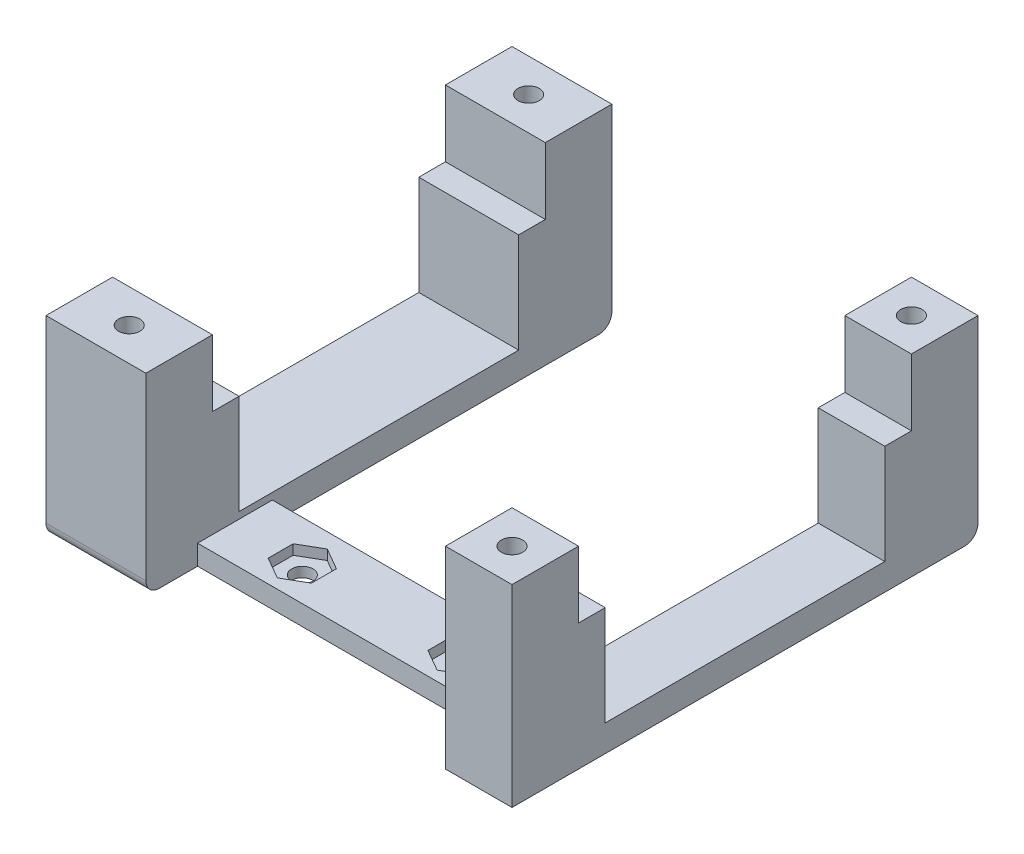
SolidWorks part; units mm, degrees
ref_plane "Alzado" through (0, 0, 0) normal (0, 0, 1) x (1, 0, 0)
ref_plane "Planta" through (0, 0, 0) normal (0, 1, 0) x (1, 0, 0)
ref_plane "Vista lateral" through (0, 0, 0) normal (1, 0, 0) x (0, 0, -1)
sketch "Croquis1" plane through (0, 0, 0) normal (0, 1, 0) x (1, 0, 0)
  line L0 (-10.4545, 22.1503) -> (-10.4545, -47.8497)
  line L1 (-25.4545, 22.1503) -> (-10.4545, 22.1503)
  line L2 (-25.4545, 22.1503) -> (-25.4545, -47.8497)
  line L3 (-25.4545, -47.8497) -> (-10.4545, -47.8497)
  line L4 (44.5455, 22.1503) -> (44.5455, -47.8497)
  line L5 (34.5455, 22.1503) -> (34.5455, -47.8497)
  line L6 (-25.4545, 12.1503) -> (-10.4545, 12.1503)
  line L7 (-25.4545, -37.8497) -> (-10.4545, -37.8497)
  line L8 (-25.4545, -47.8497) -> (-10.4545, -37.8497) construction
  line L9 (-10.4545, -37.8497) -> (-10.4545, 22.1503) construction
  line L10 (-10.4545, 22.1503) -> (-25.4545, 12.1503) construction
  line L11 (44.5455, 22.1503) -> (34.5455, 12.1503) construction
  line L12 (44.5455, -37.8497) -> (34.5455, -47.8497) construction
  line L13 (34.5455, 22.1503) -> (44.5455, 22.1503)
  line L14 (34.5455, 12.1503) -> (44.5455, 12.1503)
  line L15 (34.5455, -37.8497) -> (44.5455, -37.8497)
  line L16 (34.5455, -47.8497) -> (44.5455, -47.8497)
  circle A0 centre (-17.9545, -42.8497) radius 1.6
  circle A1 centre (-17.9545, 17.1503) radius 1.6
  circle A2 centre (39.5455, 17.1503) radius 1.6
  circle A3 centre (39.5455, -42.8497) radius 1.6
  dimension "D1" = 70
  dimension "D2" = 70
  dimension "D3" = 15
  dimension "D4" = 10
  dimension "D5" = 10
  dimension "D6" = 10
extrude "Saliente-Extruir2" add sketch "Croquis1" along normal blind 25 contours L2 L6 L0 L1 A1 | L7 L2 L3 L0 A0 | L5 L16 L4 L15 A3 | L5 L14 L4 L13 A2 region at (-10.6348, 0, -17.1503) region at (-10.6348, 0, 42.8497) region at (44.404, 0, -17.1503) region at (44.404, 0, 42.8497)
sketch "Croquis2" plane through (0, 0, 0) normal (0, -1, 0) x (1, 0, 0)
  line L0 (34.5455, -22.1503) -> (34.5455, -12.1503) construction
  line L1 (-10.4545, -22.1503) -> (-10.4545, 47.8497)
  line L2 (44.5455, -22.1503) -> (44.5455, -12.1503) construction
  line L3 (34.5455, -22.1503) -> (44.5455, -22.1503) construction
  line L4 (34.5455, 47.8497) -> (44.5455, 47.8497) construction
  line L5 (34.5455, 37.8497) -> (34.5455, 47.8497) construction
  line L6 (-25.4545, -22.1503) -> (-25.4545, 47.8497)
  line L7 (44.5455, 37.8497) -> (44.5455, 47.8497) construction
  line L8 (-25.4545, 47.8497) -> (-10.4545, 47.8497) construction
  line L9 (-25.4545, 37.8497) -> (-25.4545, 47.8497) construction
  line L10 (-10.4545, 37.8497) -> (-10.4545, 47.8497) construction
  line L13 (-25.4545, -22.1503) -> (-25.4545, -12.1503) construction
  line L14 (-25.4545, -22.1503) -> (-10.4545, -22.1503) construction
  line L15 (-10.4545, -22.1503) -> (-10.4545, -12.1503) construction
  line L16 (34.5455, -22.1503) -> (34.5455, -12.1503)
  line L17 (-10.4545, 37.8497) -> (-10.4545, 47.8497)
  line L18 (44.5455, -22.1503) -> (44.5455, -12.1503)
  line L19 (34.5455, -22.1503) -> (44.5455, -22.1503)
  line L20 (34.5455, 47.8497) -> (44.5455, 47.8497)
  line L21 (34.5455, 37.8497) -> (34.5455, 47.8497)
  line L23 (44.5455, 37.8497) -> (44.5455, 47.8497)
  line L24 (-25.4545, 47.8497) -> (-10.4545, 47.8497)
  line L25 (-25.4545, 37.8497) -> (-25.4545, 47.8497)
  line L26 (-10.4545, 37.8497) -> (-10.4545, 47.8497)
  line L29 (-25.4545, -22.1503) -> (-25.4545, -12.1503)
  line L30 (-25.4545, -22.1503) -> (-10.4545, -22.1503)
  line L31 (-10.4545, -22.1503) -> (-10.4545, -12.1503)
  line L32 (-25.4545, -22.1503) -> (-25.4545, 47.8497)
  line L33 (-10.4545, 47.8497) -> (-10.4545, -22.1503)
  line L34 (34.5455, 47.8497) -> (34.5455, -22.1503)
  line L35 (44.5455, -22.1503) -> (44.5455, 47.8497)
  circle A1 centre (-17.9545, 42.8497) radius 1.6
  circle A2 centre (-17.9545, 42.8497) radius 1.6
  circle A3 centre (-17.9545, -17.1503) radius 1.6
  circle A4 centre (-17.9545, -17.1503) radius 1.6
  circle A5 centre (39.5455, 42.8497) radius 1.6
  circle A6 centre (39.5455, 42.8497) radius 1.6
  circle A7 centre (39.5455, -17.1503) radius 1.6
  circle A8 centre (39.5455, -17.1503) radius 1.6
  circle M5 centre (-17.9545, 42.8497) radius 1.6
  line M6 (-25.4545, 37.8497) -> (-10.4545, 37.8497)
  line M7 (-10.4545, 37.8497) -> (-10.4545, 47.8497)
  line M8 (-10.4545, 47.8497) -> (-25.4545, 47.8497)
  line M9 (-25.4545, 47.8497) -> (-25.4545, 37.8497)
  dimension "D1" = 0
  dimension "D2" = 0
  dimension "D3" = 0
  dimension "D4" = 0
extrude "Saliente-Extruir3" add sketch "Croquis2" along normal blind 4 contours L6 L30 L1 A4 M6 | M9 M6 M7 M8 M5 | L18 L35 L23 L20 L21 L34 L16 L19 A8 A6 region at (-17.9545, 0, 8.0751) region at (-17.9545, 0, 38.0299) region at (39.5455, 0, 12.8497)
sketch "Croquis3" plane through (0, 0, 0) normal (0, 1, 0) x (1, 0, 0)
  line L0 (-25.4545, 12.1503) -> (-25.4545, -37.8497) construction
  line L1 (-25.4545, -37.8497) -> (-10.4545, -37.8497) construction
  line L2 (-10.4545, -37.8497) -> (-10.4545, 12.1503) construction
  line L3 (-10.4545, 12.1503) -> (-25.4545, 12.1503) construction
  line L4 (44.5455, 12.1503) -> (34.5455, 12.1503) construction
  line L5 (34.5455, 12.1503) -> (34.5455, -37.8497) construction
  line L6 (34.5455, -37.8497) -> (44.5455, -37.8497) construction
  line L7 (44.5455, -37.8497) -> (44.5455, 12.1503) construction
  line L8 (-25.4545, 12.1503) -> (-25.4545, 8.1503)
  line L9 (-25.4545, -37.8497) -> (-10.4545, -37.8497)
  line L10 (-10.4545, -37.8497) -> (-10.4545, -33.8497)
  line L11 (-10.4545, 12.1503) -> (-25.4545, 12.1503)
  line L12 (44.5455, 12.1503) -> (34.5455, 12.1503)
  line L13 (34.5455, 12.1503) -> (34.5455, 8.1503)
  line L14 (34.5455, -37.8497) -> (44.5455, -37.8497)
  line L15 (44.5455, -37.8497) -> (44.5455, -33.8497)
  line L16 (-25.4545, 8.1503) -> (-10.4545, 8.1503)
  line L17 (-25.4545, -37.8497) -> (-10.4545, -37.8497)
  line L18 (-25.4545, -37.8497) -> (-25.4545, -33.8497)
  line L19 (-25.4545, -33.8497) -> (-10.4545, -33.8497)
  line L20 (-10.4545, -37.8497) -> (-10.4545, -33.8497)
  line L21 (34.5455, -33.8497) -> (44.5455, -33.8497)
  line L22 (34.5455, 8.1503) -> (44.5455, 8.1503)
  line L23 (34.5455, -33.8497) -> (34.5455, -37.8497)
  line L24 (44.5455, 8.1503) -> (44.5455, 12.1503)
  line L25 (-10.4545, 8.1503) -> (-10.4545, 12.1503)
  line L26 (-25.4545, -33.8497) -> (-25.4545, -37.8497)
  line M8 (44.5455, 12.1503) -> (34.5455, 12.1503)
  line M9 (34.5455, 12.1503) -> (34.5455, -37.8497)
  line M10 (34.5455, -37.8497) -> (44.5455, -37.8497)
  line M11 (44.5455, -37.8497) -> (44.5455, 12.1503)
  dimension "D1" = 4
  dimension "D2" = 4
extrude "Saliente-Extruir4" add sketch "Croquis3" along normal blind 15 contours L19 L18 L9 L10 | L16 L25 L11 L8 | L22 M9 M11 M8 | L21 M9 M10 M11 region at (-17.9545, 0, -10.1503) region at (-17.9545, 0, 35.8497) region at (39.5455, 0, -10.1503) region at (39.5455, 0, 35.8497)
sketch "Croquis4" plane through (0, -4, 0) normal (0, -1, 0) x (1, 0, 0)
  circle A8 centre (39.5455, 42.8497) radius 3.5
  circle A9 centre (39.5455, -17.1503) radius 3.5
  circle A10 centre (-17.9545, -17.1503) radius 3.5
  circle A11 centre (-17.9545, 42.8497) radius 3.5
  dimension "D1" = 7
  dimension "D2" = 7
  dimension "D3" = 7
  dimension "D4" = 7
extrude "Cortar-Extruir1" cut sketch "Croquis4" against normal blind 3.5
sketch "Croquis5" plane through (0, -4, 0) normal (0, -1, 0) x (1, 0, 0)
  line L0 (-10.4545, -22.1503) -> (-10.4545, 47.8497) construction
  line L1 (-10.4545, 40.0798) -> (34.5455, 40.0798)
  line L2 (34.5455, 40.0798) -> (34.5455, 35.8497)
  line L4 (-10.4545, 40.0798) -> (-10.4545, 35.8497)
  line L5 (-10.4545, 28.8497) -> (34.5455, 28.8497)
  line L6 (34.5455, -22.1503) -> (34.5455, 47.8497) construction
  line L7 (-10.4545, 35.8497) -> (-10.4545, 28.8497)
  line L8 (34.5455, 35.8497) -> (34.5455, 28.8497)
extrude "Saliente-Extruir5" add sketch "Croquis5" against normal blind 3
sketch "Croquis6" plane through (0, -4, 0) normal (0, -1, 0) x (1, 0, 0)
  line L0 (-10.4545, 28.8497) -> (34.5455, 28.8497) construction
  line L3 (34.5455, 34.8497) -> (22.4455, 34.8497) construction
  line L4 (1.6455, 34.8497) -> (-10.4545, 34.8497) construction
  circle A0 centre (24.0455, 34.8497) radius 1.6
  circle A1 centre (0.0455, 34.8497) radius 1.6
  dimension "D1" = 6
  dimension "D2" = 24
extrude "Cortar-Extruir2" cut sketch "Croquis6" against normal blind 3
sketch "Croquis7" plane through (0, -1, 0) normal (0, 1, 0) x (1, 0, 0)
  line L0 (-10.4545, -28.8497) -> (34.5455, -28.8497) construction
  line L1 (0.0455, -31.0969) -> (-3.2045, -32.9733)
  line L2 (-3.2045, -32.9733) -> (-3.2045, -36.726)
  line L3 (-3.2045, -36.726) -> (0.0455, -38.6024)
  line L4 (0.0455, -38.6024) -> (3.2955, -36.726)
  line L5 (3.2955, -36.726) -> (3.2955, -32.9733)
  line L6 (3.2955, -32.9733) -> (0.0455, -31.0969)
  line L7 (24.0455, -31.0969) -> (20.7955, -32.9733)
  line L8 (20.7955, -32.9733) -> (20.7955, -36.726)
  line L9 (20.7955, -36.726) -> (24.0455, -38.6024)
  line L10 (24.0455, -38.6024) -> (27.2955, -36.726)
  line L11 (27.2955, -36.726) -> (27.2955, -32.9733)
  line L12 (27.2955, -32.9733) -> (24.0455, -31.0969)
  circle A5 centre (0.0455, -34.8497) radius 3.25 construction
  circle A6 centre (24.0455, -34.8497) radius 3.25 construction
  dimension "D1" = 6.5
  dimension "D2" = 24
  dimension "D3" = 6
extrude "Cortar-Extruir3" cut sketch "Croquis7" against normal blind 1.5
fillet "Redondeo1" radius 2 3 edges at (-17.9545, -4, 47.8497) (-17.9545, -4, -22.1503) (39.5455, -4, -22.1503)
